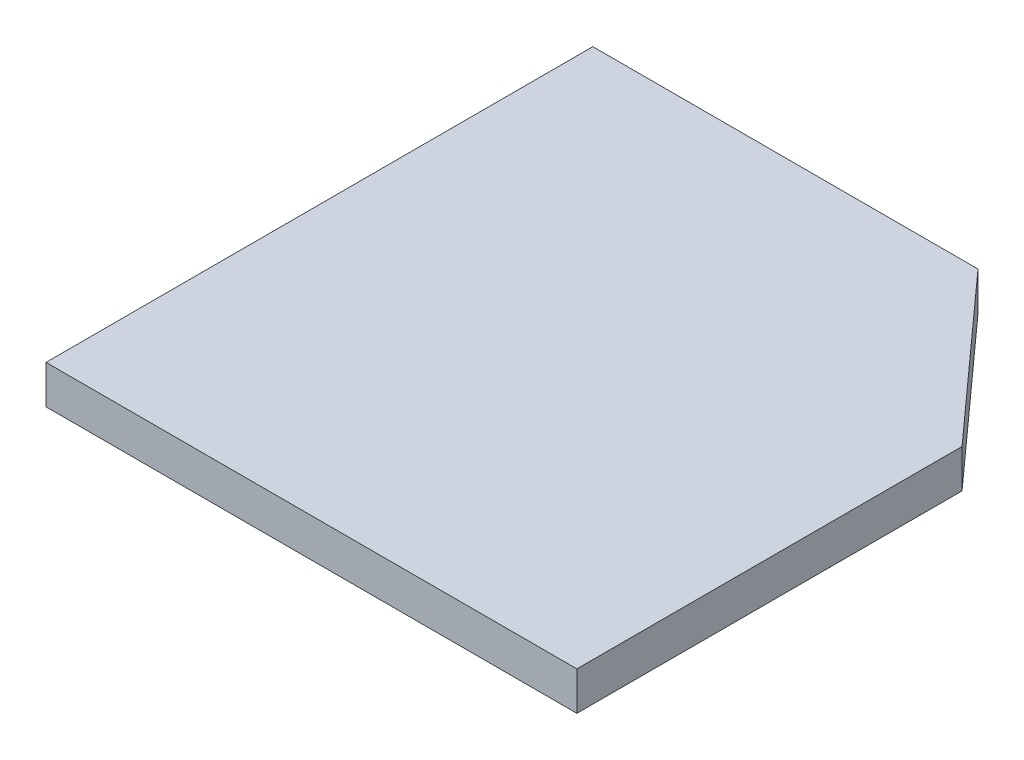
SolidWorks part; units mm, degrees
ref_plane "Спереди" through (0, 0, 0) normal (0, 0, 1) x (1, 0, 0)
ref_plane "Сверху" through (0, 0, 0) normal (0, 1, 0) x (1, 0, 0)
ref_plane "Справа" through (0, 0, 0) normal (1, 0, 0) x (0, 0, -1)
sketch "Эскиз1" plane through (0, 0, 0) normal (0, 1, 0) x (1, 0, 0)
  line L0 (0, 0) -> (68.9142, 0)
  line L1 (0, 0) -> (0, 70.9877)
  line L2 (68.9142, 0) -> (68.9142, 50)
  line L3 (0, 70.9877) -> (50, 70.9877)
  line L4 (50, 70.9877) -> (68.9142, 50)
  point P7 (0.6283, 70.7034)
extrude "Бобышка-Вытянуть1" add sketch "Эскиз1" along normal blind 5
